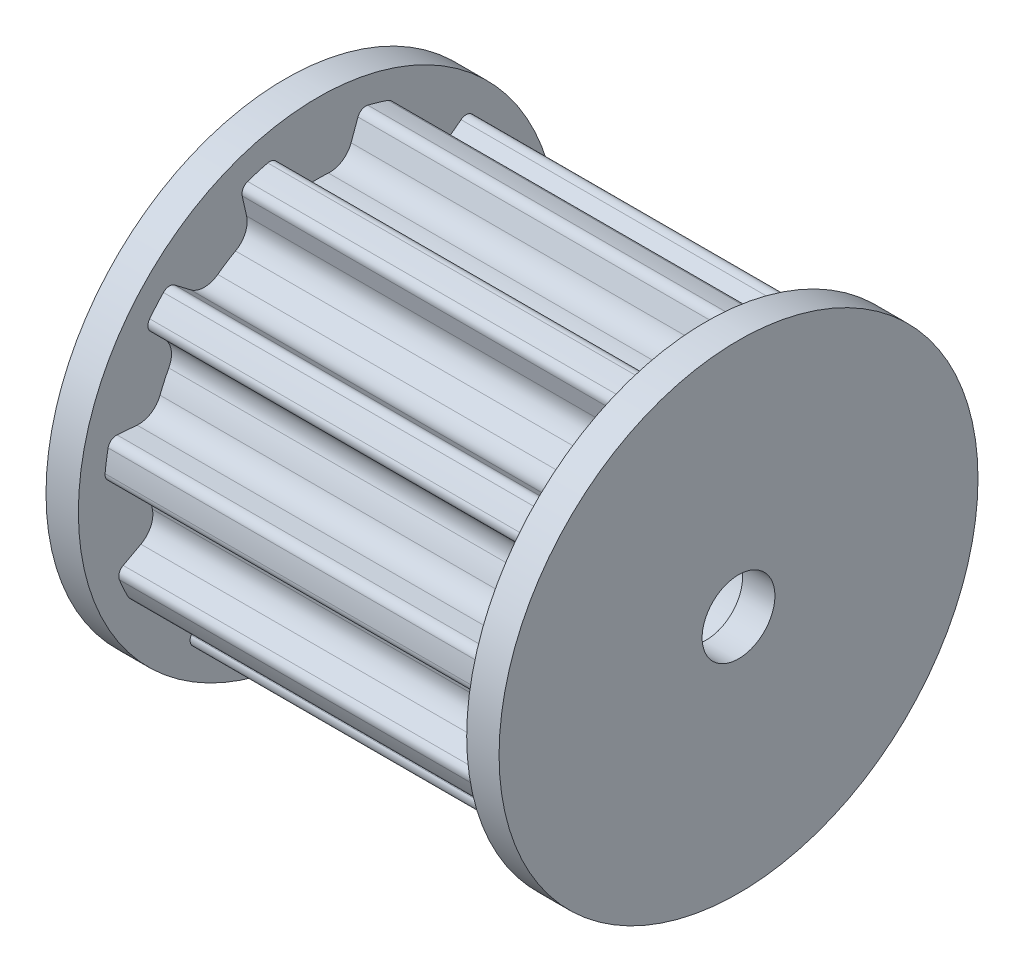
SolidWorks part; units mm, degrees
material "尼龙 6/10"
ref_plane "前视基准面" through (0, 0, 0) normal (0, 0, 1) x (1, 0, 0)
ref_plane "上视基准面" through (0, 0, 0) normal (0, 1, 0) x (1, 0, 0)
ref_plane "右视基准面" through (0, 0, 0) normal (1, 0, 0) x (0, 0, -1)
sketch "草图1" plane through (0, 0, 0) normal (0, 0, 1) x (1, 0, 0)
  line L0 (0, 0) -> (64.8368, 0) construction
  line L1 (0, 1) -> (0, 3.301)
  line L2 (0, 3.301) -> (6, 3.301)
  line L3 (6, 3.301) -> (6, 2.2264)
  line L6 (6, 1) -> (0, 1)
  line L10 (6, 2.2264) -> (6, 1)
  dimension "B" = 6
  dimension "d" = 2
  dimension "da" = 6.602
revolve "旋转1" add sketch "草图1" angle 360 about L0
ref_axis "基准轴1" through (-72.504, 0, 0) along (1, 0, 0)
sketch "草图6" plane through (0, 0, 0) normal (1, 0, 0) x (0, 0, -1)
  line L0 (0, 0) -> (0, 16.0158) construction
  line L1 (0.6203, 3.1273) -> (0.5141, 2.8355)
  line L2 (0.8987, 3.1763) -> (1.3968, 4.5448)
  line L3 (-0.8987, 3.1763) -> (-1.3968, 4.5448)
  line L4 (-0.6203, 3.1273) -> (-0.5141, 2.8355)
  circle A0 centre (0, 0) radius 3.301 construction
  arc A1 (0.1633, 2.6059) -> (-0.1633, 2.6059) centre (0, 0) ccw
  arc A2 (0.7729, 3.2092) -> (0.8987, 3.1763) centre (0, 0) cw
  arc A3 (0.5141, 2.8355) -> (0.1633, 2.6059) centre (0.1852, 2.9552) cw
  arc A4 (0.6203, 3.1273) -> (0.7729, 3.2092) centre (0.7425, 3.0829) cw
  arc A5 (1.3968, 4.5448) -> (-1.3968, 4.5448) centre (0, 0) ccw
  arc A6 (-0.7729, 3.2092) -> (-0.8987, 3.1763) centre (0, 0) ccw
  arc A7 (-0.6203, 3.1273) -> (-0.7729, 3.2092) centre (-0.7425, 3.0829) ccw
  arc A8 (-0.5141, 2.8355) -> (-0.1633, 2.6059) centre (-0.1852, 2.9552) ccw
  point P8 (0, 15.3258)
  point P14 (0.6593, 3.2345)
  point P16 (0.42, 2.577)
  dimension "D1" = 2.611
  dimension "ra" = 0.13
  dimension "rf" = 0.35
  dimension "D3" = 1.4563
  dimension "D4" = 0.13
  dimension "bw" = 0.84
  dimension "angle" = 40
  dimension "hg" = 0.69
extrude "切除-拉伸2" cut sketch "草图6" along normal up to next
pattern_circular "阵列(圆周)3" count 11 over 360 about axis through (-72.504, 0, 0) along (1, 0, 0) of "切除-拉伸2"
sketch "草图7" plane through (0, 0, 0) normal (-1, 0, 0) x (0, 0, 1)
  circle A0 centre (0, 0) radius 3.7
  dimension "D1" = 7.4
extrude "凸台-拉伸1" add sketch "草图7" along normal blind 0.5
sketch "草图8" plane through (-0.5, 0, 0) normal (-1, 0, 0) x (0, 0, 1)
  circle A0 centre (0, 0) radius 1.75
  dimension "D1" = 3.5
extrude "切除-拉伸3" cut sketch "草图8" against normal blind 0.25
sketch "草图9" plane through (6, 0, 0) normal (1, 0, 0) x (0, 0, -1)
  circle A0 centre (0, 0) radius 3.7
  dimension "D1" = 7.4
extrude "凸台-拉伸2" add sketch "草图9" along normal blind 0.5
sketch "草图11" plane through (-0.25, 0, 0) normal (-1, 0, 0) x (0, 0, 1)
  circle A0 centre (0, 0) radius 1.55
  dimension "D1" = 3.1
extrude "切除-拉伸5" cut sketch "草图11" against normal blind 3
sketch "草图13" plane through (6.5, 0, 0) normal (1, 0, 0) x (0, 0, -1)
  circle A0 centre (0, 0) radius 0.5625
  dimension "D1" = 1.125
extrude "切除-拉伸7" cut sketch "草图13" against normal through all
equation "\"D4@草图6\" = \"ra@草图6\""
equation "\"D1@草图6\" = \"da@草图1\" / 2 - \"hg@草图6\" "
